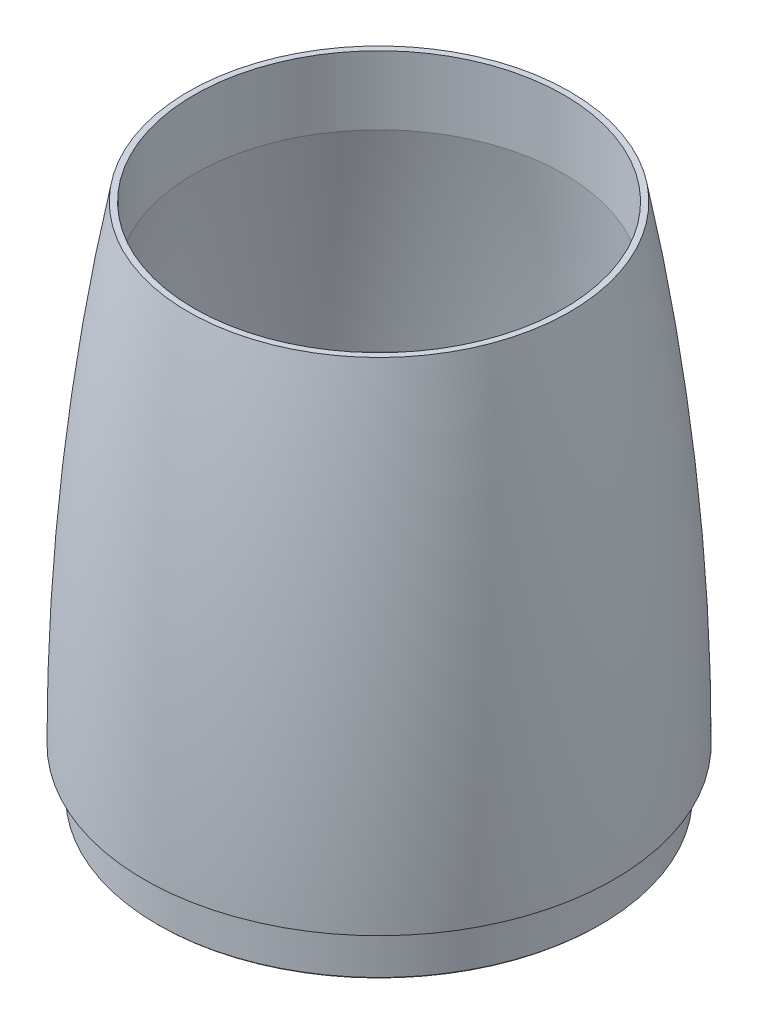
SolidWorks part; units mm, degrees
ref_plane "Front Plane" through (0, 0, 0) normal (0, 0, 1) x (1, 0, 0)
ref_plane "Top Plane" through (0, 0, 0) normal (0, 1, 0) x (1, 0, 0)
ref_plane "Right Plane" through (0, 0, 0) normal (1, 0, 0) x (0, 0, -1)
sketch "Sketch1" plane through (0, 0, 0) normal (0, 0, 1) x (1, 0, 0)
  line L0 (0, -1572.0261) -> (0, 77082.0793) construction
  line L1 (-32.5, 80) -> (-31.5, 80)
  line L2 (-31.5, 80) -> (-31.5, 68.3472)
  line L3 (0, 0) -> (-40, 0) construction
  line L4 (-40, -986.4994) -> (-40, 49013.5006) construction
  line L5 (-40, 0) -> (-37.75, 0)
  line L6 (-37.75, 0) -> (-37.75, -8)
  line L7 (-37.75, -8) -> (-35.75, -8)
  line L8 (-35.75, -8) -> (-35.75, 32.6646)
  arc A0 (-32.5, 80) -> (-40, 0) centre (390.4167, 0) ccw
  arc A1 (-31.5, 68.3472) -> (-35.75, 32.6646) centre (390.4167, 0) ccw
  dimension "D2" = 3
  dimension "D1" = 80
  dimension "D3" = 63
  dimension "D4" = 1
  dimension "D5" = 80
  dimension "D6" = 75.5
  dimension "D7" = 2
  dimension "D8" = 8
revolve "Revolve1" add sketch "Sketch1" angle 360 about L0
chamfer "Chamfer1" distance 0.25 angle 45 2 edges at (0, -8, -37.75) (0, -8, -35.75)
